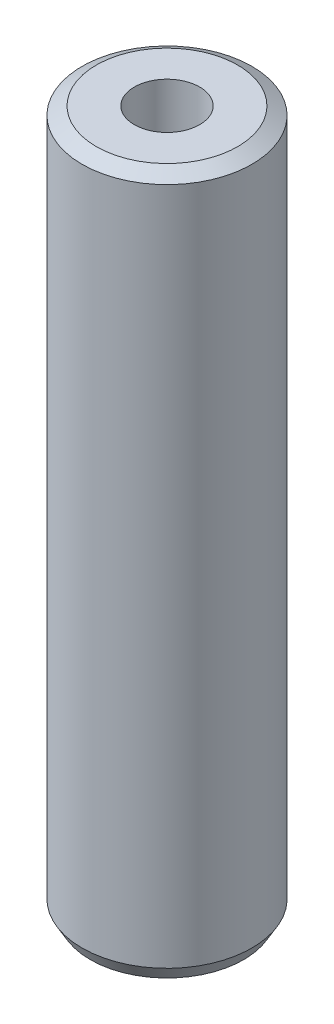
SolidWorks part; units mm, degrees
ref_plane "Front Plane" through (0, 0, 0) normal (0, 0, 1) x (1, 0, 0)
ref_plane "Top Plane" through (0, 0, 0) normal (0, 1, 0) x (1, 0, 0)
ref_plane "Right Plane" through (0, 0, 0) normal (1, 0, 0) x (0, 0, -1)
sketch "Sketch1" plane through (0, 0, 0) normal (0, 1, 0) x (1, 0, 0)
  circle A0 centre (0, 0) radius 45
  dimension "SHAFT_OD" = 90
extrude "Boss-Extrude1" add sketch "Sketch1" along normal blind 371.5313
sketch "Sketch2" plane through (0, 0, 0) normal (0, 1, 0) x (1, 0, 0)
  circle A0 centre (0, 0) radius 17.3186
  dimension "BORE_D" = 34.6371
extrude "Cut-Extrude1" cut sketch "Sketch2" along normal through all
chamfer "Chamfer1" distance 4.3482 angle 60 2 edges at (0, 371.5313, 45) (0, 0, 45) first distance on face at (0, 371.5313, 45) first distance on face at (0, 0, 17.3186)
